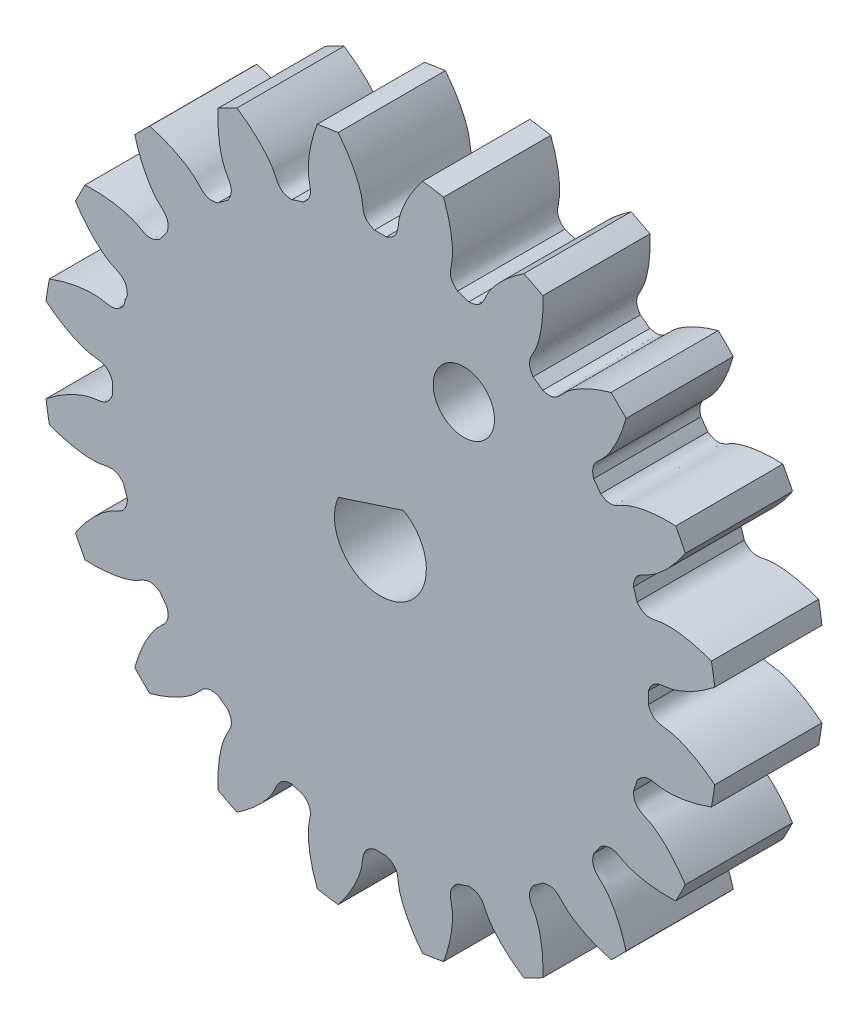
SolidWorks part; units mm, degrees
ref_plane "前视基准面" through (0, 0, 0) normal (0, 0, 1) x (1, 0, 0)
ref_plane "上视基准面" through (0, 0, 0) normal (0, 1, 0) x (1, 0, 0)
ref_plane "右视基准面" through (0, 0, 0) normal (1, 0, 0) x (0, 0, -1)
sketch "草图1" plane through (0, 0, 0) normal (0, 0, 1) x (1, 0, 0)
  circle A0 centre (0, 0) radius 22
extrude "凸台-拉伸1" add sketch "草图1" along normal blind 7
ref_axis "基准轴1" through (0, 0, -0.25) along (0, 0, 1)
sketch "草图2" plane through (0, 0, 0) normal (0, 0, 1) x (1, 0, 0)
  line L0 (0, 0) -> (0, 22) construction
  circle A0 centre (0, 0) radius 22 construction
  arc A1 (0.3866, 17.4957) -> (-0.3866, 17.4957) centre (0, 0) ccw
  arc A2 (6.3623, 24.9965) -> (-6.3623, 24.9965) centre (0, 0) ccw
  spline S0 degree 3 poles (0.3866, 17.4957) (1.2224, 17.787) (1.1142, 18.3742) (1.2258, 18.94) (1.2378, 18.9951) (1.2526, 19.0573) (1.2706, 19.1264) (1.292, 19.2024) (1.317, 19.2851) (1.3461, 19.3745) (1.3793, 19.4704) (1.4171, 19.5726) (1.4597, 19.6811) (1.5073, 19.7956) (1.5603, 19.9161) (1.6187, 20.0423) (1.683, 20.174) (1.7534, 20.3112) (1.83, 20.4535) (1.9132, 20.6008) (2.0031, 20.7529) (2.1, 20.9095) (2.204, 21.0705) (2.3155, 21.2356) (2.4346, 21.4046) (2.5615, 21.5772) (2.6964, 21.7533) (2.8395, 21.9324) (2.991, 22.1145) (3.1509, 22.2992) (3.3196, 22.4862) (3.4971, 22.6753) (3.6837, 22.8662) (3.8793, 23.0586) (4.0843, 23.2521) (4.2986, 23.4467) (4.5225, 23.6418) (4.7559, 23.8372) (4.9991, 24.0327) (5.2521, 24.2278) (5.515, 24.4223) (5.8829, 24.6833) (6.1679, 24.8727) (6.3623, 24.9965) knots 0 0 0 0 0.165916 0.170906 0.176664 0.183189 0.190482 0.198542 0.207371 0.216967 0.22733 0.238462 0.250361 0.263027 0.276462 0.290664 0.305634 0.321371 0.337876 0.355149 0.37319 0.391998 0.411574 0.431917 0.453028 0.474907 0.497554 0.520968 0.54515 0.570099 0.595817 0.622302 0.649554 0.677575 0.706363 0.735918 0.766242 0.797333 0.829191 0.861818 0.895212 0.929373 1 1 1 1
  spline S1 degree 3 poles (-0.3866, 17.4957) (-1.2224, 17.787) (-1.1142, 18.3742) (-1.2258, 18.94) (-1.2378, 18.9951) (-1.2526, 19.0573) (-1.2706, 19.1264) (-1.292, 19.2024) (-1.317, 19.2851) (-1.3461, 19.3745) (-1.3793, 19.4704) (-1.4171, 19.5726) (-1.4597, 19.6811) (-1.5073, 19.7956) (-1.5603, 19.9161) (-1.6187, 20.0423) (-1.683, 20.174) (-1.7534, 20.3112) (-1.83, 20.4535) (-1.9132, 20.6008) (-2.0031, 20.7529) (-2.1, 20.9095) (-2.204, 21.0705) (-2.3155, 21.2356) (-2.4346, 21.4046) (-2.5615, 21.5772) (-2.6964, 21.7533) (-2.8395, 21.9324) (-2.991, 22.1145) (-3.1509, 22.2992) (-3.3196, 22.4862) (-3.4971, 22.6753) (-3.6837, 22.8662) (-3.8793, 23.0586) (-4.0843, 23.2521) (-4.2986, 23.4467) (-4.5225, 23.6418) (-4.7559, 23.8372) (-4.9991, 24.0327) (-5.2521, 24.2278) (-5.515, 24.4223) (-5.8829, 24.6833) (-6.1679, 24.8727) (-6.3623, 24.9965) knots 0 0 0 0 0.165916 0.170906 0.176664 0.183189 0.190482 0.198542 0.207371 0.216967 0.22733 0.238462 0.250361 0.263027 0.276462 0.290664 0.305634 0.321371 0.337876 0.355149 0.37319 0.391998 0.411574 0.431917 0.453028 0.474907 0.497554 0.520968 0.54515 0.570099 0.595817 0.622302 0.649554 0.677575 0.706363 0.735918 0.766242 0.797333 0.829191 0.861818 0.895212 0.929373 1 1 1 1
extrude "切除-拉伸1" cut sketch "草图2" along normal through all
pattern_circular "阵列(圆周)1" count 20 every 18 about axis through (0, 0, -0.25) along (0, 0, 1) of "切除-拉伸1"
sketch "草图3" plane through (0, 0, 0) normal (0, 0, 1) x (1, 0, 0)
  circle A0 centre (0, 0) radius 20 construction
  dimension "Dn" = 40
sketch "草图4" plane through (0, 0, 7) normal (0, 0, 1) x (1, 0, 0)
  line L0 (1.5086, 2.5931) -> (-2.7447, 1.2111)
  line L1 (0, 0) -> (-3.1538, 9.7064) construction
  line L2 (5.4479, 10.6921) -> (0, 0) construction
  line L3 (-5.0388, 16.7589) -> (-5.7742, 16.52) construction
  arc A0 (-2.7447, 1.2111) -> (1.5086, 2.5931) centre (0, 0) ccw
  circle A5 centre (5.4479, 10.6921) radius 2
  point P5 (85.1103, 44.6908)
  dimension "D1" = 6
  dimension "D3" = 45
  dimension "D4" = 4
  dimension "D2" = 12
  dimension "D9" = 2
extrude "切除-拉伸2" cut sketch "草图4" against normal blind 10
